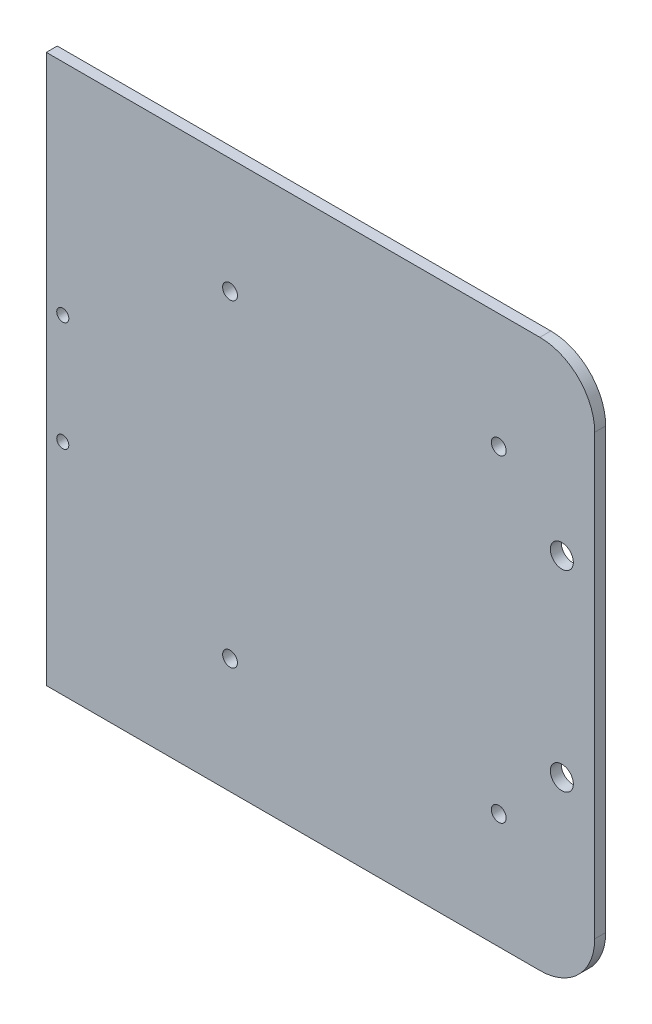
SolidWorks part; units mm, degrees
ref_plane "前视基准面" through (0, 0, 0) normal (0, 0, 1) x (1, 0, 0)
ref_plane "上视基准面" through (0, 0, 0) normal (0, 1, 0) x (1, 0, 0)
ref_plane "右视基准面" through (0, 0, 0) normal (1, 0, 0) x (0, 0, -1)
sketch "草图1" plane through (0, 0, 0) normal (0, 0, 1) x (1, 0, 0)
  line L0 (50, 0) -> (-50, 0) construction
  line L1 (-50, 50) -> (40, 50)
  line L2 (-50, 50) -> (-50, -50)
  line L3 (-50, -50) -> (40, -50)
  line L4 (50, 40) -> (50, -40)
  line L5 (-50, 50) -> (50, -50) construction
  line L6 (-50, -50) -> (50, 50) construction
  circle A0 centre (-47, 10) radius 1.1
  circle A1 centre (-47, -10) radius 1.1
  arc A2 (40, 50) -> (50, 40) centre (40, 40) cw
  arc A3 (50, -40) -> (40, -50) centre (40, -40) cw
  point P0 (0, 0)
  dimension "D3" = 2.2
  dimension "D4" = 20
  dimension "D5" = 3
  dimension "D6" = 10
  dimension "D1" = 100
  dimension "D2" = 100
extrude "凸台-拉伸1" add sketch "草图1" along normal blind 2
sketch "草图3" plane through (0, 0, 2) normal (0, 0, 1) x (1, 0, 0)
  line L0 (-50, 0) -> (50, 0) construction
  line L1 (-16.5, -50) -> (-16.5, 50) construction
  line L2 (8, -50) -> (8, 50) construction
  line L3 (32.5, -50) -> (32.5, 50) construction
  line L4 (50, -40) -> (50, 40)
  line L5 (40, 50) -> (-50, 50)
  line L6 (-50, 50) -> (-50, -50)
  line L7 (-50, -50) -> (40, -50)
  line L8 (50, -40) -> (50, 40)
  line L9 (40, 50) -> (-50, 50)
  line L10 (-50, 50) -> (-50, -50)
  line L11 (-50, -50) -> (40, -50)
  circle A0 centre (-16.5, -29) radius 1.35
  circle A1 centre (-16.5, 29) radius 1.35
  circle A2 centre (32.5, 29) radius 1.35
  circle A3 centre (32.5, -29) radius 1.35
  arc A6 (40, -50) -> (50, -40) centre (40, -40) ccw
  arc A7 (40, -50) -> (50, -40) centre (40, -40) ccw
  arc A8 (50, 40) -> (40, 50) centre (40, 40) ccw
  arc A9 (50, 40) -> (40, 50) centre (40, 40) ccw
  dimension "D3" = 2.7
  dimension "D4" = 58
  dimension "D5" = 49
  dimension "D2" = 33.5
  dimension "D1" = 0
extrude "切除-拉伸1" cut sketch "草图3" against normal through all contours A0 | A1 | A2 | A3 region at (-16.5, -29, 2) region at (-16.5, 29, 2) region at (32.5, 29, 2) region at (32.5, -29, 2)
sketch "草图7" plane through (0, 0, 2) normal (0, 0, 1) x (1, 0, 0)
  line L0 (50, 0) -> (-50, 0) construction
  line L1 (44, 50) -> (44, -50) construction
  line L4 (50, -40) -> (50, 40)
  line L5 (40, 50) -> (-50, 50)
  line L6 (-50, 50) -> (-50, -50)
  line L7 (-50, -50) -> (40, -50)
  line L8 (50, -40) -> (50, 40)
  line L9 (40, 50) -> (-50, 50)
  line L10 (-50, 50) -> (-50, -50)
  line L11 (-50, -50) -> (40, -50)
  circle A0 centre (44, 17.5) radius 2.1
  circle A1 centre (44, -17.5) radius 2.1
  arc A4 (40, -50) -> (50, -40) centre (40, -40) ccw
  arc A5 (40, -50) -> (50, -40) centre (40, -40) ccw
  arc A6 (50, 40) -> (40, 50) centre (40, 40) ccw
  arc A7 (50, 40) -> (40, 50) centre (40, 40) ccw
  dimension "D3" = 4.2
  dimension "D4" = 35
  dimension "D2" = 6
  dimension "D1" = 0
extrude "切除-拉伸5" cut sketch "草图7" against normal blind 10 contours A0 | A1 region at (44, 17.5, 2) region at (44, -17.5, 2)
